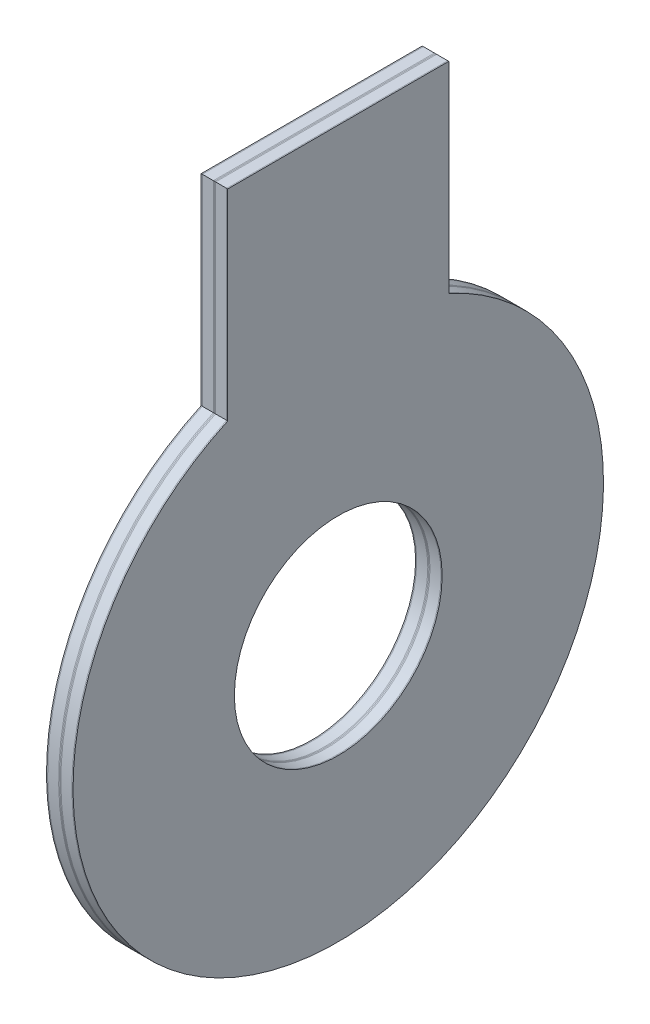
SolidWorks part; units mm, degrees
ref_plane "Front Plane" through (0, 0, 0) normal (0, 0, 1) x (1, 0, 0)
ref_plane "Top Plane" through (0, 0, 0) normal (0, 1, 0) x (1, 0, 0)
ref_plane "Right Plane" through (0, 0, 0) normal (1, 0, 0) x (0, 0, -1)
sketch "Sketch1" plane through (0, 0, 0) normal (1, 0, 0) x (0, 0, -1)
  line L0 (-25, 100) -> (25, 100)
  line L1 (-25, 100) -> (-25, 54.5436)
  line L2 (25, 100) -> (25, 54.5436)
  circle A0 centre (0, 0) radius 60
  circle A1 centre (0, 0) radius 23.5
  point P7 (0, 100)
  dimension "D1" = 120
  dimension "D2" = 47
  dimension "D3" = 40
  dimension "D4" = 50
extrude "Boss-Extrude1" add sketch "Sketch1" along normal blind 0.25 contours A0 L2 L0 L1 | A0 A1 region at (0, 79.0766, 0) region at (0, 58.3029, 0)
sketch "Sketch4" plane through (0, 0, 0) normal (-1, 0, 0) x (0, 0, 1)
  line L3 (25, 54.5436) -> (25, 100)
  line L4 (25, 100) -> (-25, 100)
  line L5 (-25, 100) -> (-25, 54.5436)
  line L6 (25, 54.5436) -> (25, 100)
  line L7 (25, 100) -> (-25, 100)
  line L8 (-25, 100) -> (-25, 54.5436)
  circle A0 centre (0, 0) radius 23.5 construction
  arc A1 (-25, 54.5436) -> (25, 54.5436) centre (0, 0) ccw
  arc A2 (-25, 54.5436) -> (25, 54.5436) centre (0, 0) ccw
  circle A3 centre (0, 0) radius 23.5
  dimension "D1" = 0
extrude "Boss-Extrude4" add sketch "Sketch4" along normal blind 2.5 separate body
sketch "Sketch5" plane through (-2.5, 0, 0) normal (-1, 0, 0) x (0, 0, 1)
  line L3 (25, 54.5436) -> (25, 100)
  line L4 (25, 100) -> (-25, 100)
  line L5 (-25, 100) -> (-25, 54.5436)
  line L6 (25, 54.5436) -> (25, 100)
  line L7 (25, 100) -> (-25, 100)
  line L8 (-25, 100) -> (-25, 54.5436)
  circle A0 centre (0, 0) radius 23.5 construction
  arc A1 (-25, 54.5436) -> (25, 54.5436) centre (0, 0) ccw
  arc A2 (-25, 54.5436) -> (25, 54.5436) centre (0, 0) ccw
  circle A3 centre (0, 0) radius 23.5
  dimension "D1" = 0
extrude "Boss-Extrude5" add sketch "Sketch5" along normal blind 0.25 separate body
sketch "Sketch10" plane through (-2.75, 0, 0) normal (-1, 0, 0) x (0, 0, 1)
  circle A1 centre (0, 0) radius 23.5
  circle A2 centre (0, 0) radius 23.5
  arc M2 (-25, 54.5436) -> (25, 54.5436) centre (0, 0) ccw
  line M3 (25, 54.5436) -> (25, 100)
  line M4 (25, 100) -> (-25, 100)
  line M5 (-25, 100) -> (-25, 54.5436)
  circle M6 centre (0, 0) radius 23.5
  dimension "D1" = 0
extrude "Boss-Extrude9" add sketch "Sketch10" along normal blind 0.25 separate body contours M5 M2 M3 M4 M6 region at (-2.75, 77.2718, -23)
sketch "Sketch11" plane through (-3, 0, 0) normal (-1, 0, 0) x (0, 0, 1)
  circle A1 centre (0, 0) radius 23.5
  circle A2 centre (0, 0) radius 23.5
  circle M2 centre (0, 0) radius 23.5
  line M3 (-25, 100) -> (-25, 54.5436)
  arc M4 (-25, 54.5436) -> (25, 54.5436) centre (0, 0) ccw
  line M5 (25, 54.5436) -> (25, 100)
  line M6 (25, 100) -> (-25, 100)
  dimension "D1" = 0
extrude "Boss-Extrude10" add sketch "Sketch11" along normal blind 2.5 separate body contours M6 M3 M4 M5 M2 region at (-3, 98, 0)
sketch "Sketch13" plane through (-5.5, 0, 0) normal (-1, 0, 0) x (0, 0, 1)
  circle A1 centre (0, 0) radius 23.5
  circle A2 centre (0, 0) radius 23.5
  line M2 (25, 100) -> (-25, 100)
  line M3 (-25, 100) -> (-25, 54.5436)
  arc M4 (-25, 54.5436) -> (25, 54.5436) centre (0, 0) ccw
  line M5 (25, 54.5436) -> (25, 100)
  circle M6 centre (0, 0) radius 23.5
  dimension "D1" = 0
extrude "Boss-Extrude11" add sketch "Sketch13" along normal blind 0.25 separate body contours M5 M2 M3 M4 M6 region at (-5.5, 77.2718, 23)
